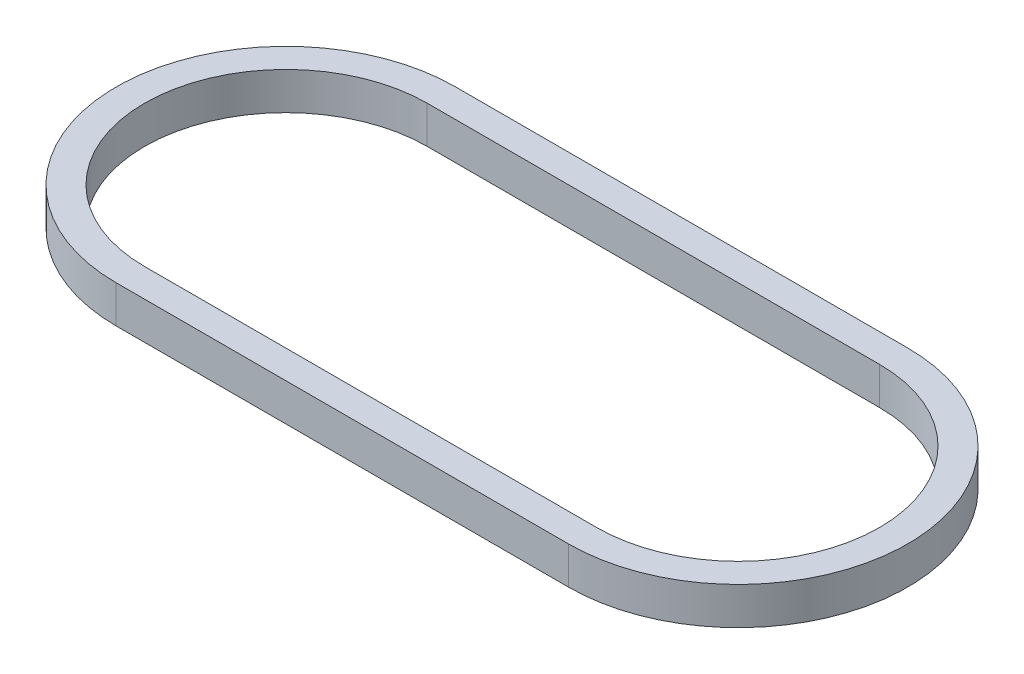
SolidWorks part; units mm, degrees
material "6061 Alloy"
ref_plane "Front Plane" through (0, 0, 0) normal (0, 0, 1) x (1, 0, 0)
ref_plane "Top Plane" through (0, 0, 0) normal (0, 1, 0) x (1, 0, 0)
ref_plane "Right Plane" through (0, 0, 0) normal (1, 0, 0) x (0, 0, -1)
sketch "Sketch1" plane through (0, 0, 0) normal (0, 1, 0) x (1, 0, 0)
  line L0 (-47.1, 0) -> (47.1, 0) construction
  line L1 (-47.1, 0) -> (47.1, 0) construction
  line L3 (-47.1, -35.3387) -> (47.1, -35.3387)
  line L4 (-47.1, 0) -> (47.1, 0) construction
  line L6 (-47.1, -29.4459) -> (47.1, -29.4459)
  line L7 (-47.1, 29.4459) -> (-47.1, 35.3387) construction
  line L8 (0, 0) -> (0, 18) construction
  line L9 (-47.1, 35.3387) -> (47.1, 35.3387)
  line L14 (-47.1, 29.4459) -> (47.1, 29.4459)
  arc A0 (-47.1, 35.3387) -> (-47.1, -35.3387) centre (-47.1, 0) ccw
  arc A1 (47.1, -35.3387) -> (47.1, 35.3387) centre (47.1, 0) ccw
  arc A2 (-47.1, 29.4459) -> (-47.1, -29.4459) centre (-47.1, 0) ccw
  arc A3 (47.1, -29.4459) -> (47.1, 29.4459) centre (47.1, 0) ccw
  point P0 (0, 0)
  point P4 (0, 0)
  point P10 (0, 0)
  point P18 (-47.1, 32.3923)
  dimension "D2" = 32.3923
  dimension "D3" = 5.8928
  dimension "D1" = 94.2
  dimension "D5" = 18
extrude "Boss-Extrude1" add sketch "Sketch1" along normal blind 7.7978 contours A0 L3 A1 A3 L6 A2 region at (-80.6448, 0, 0)
